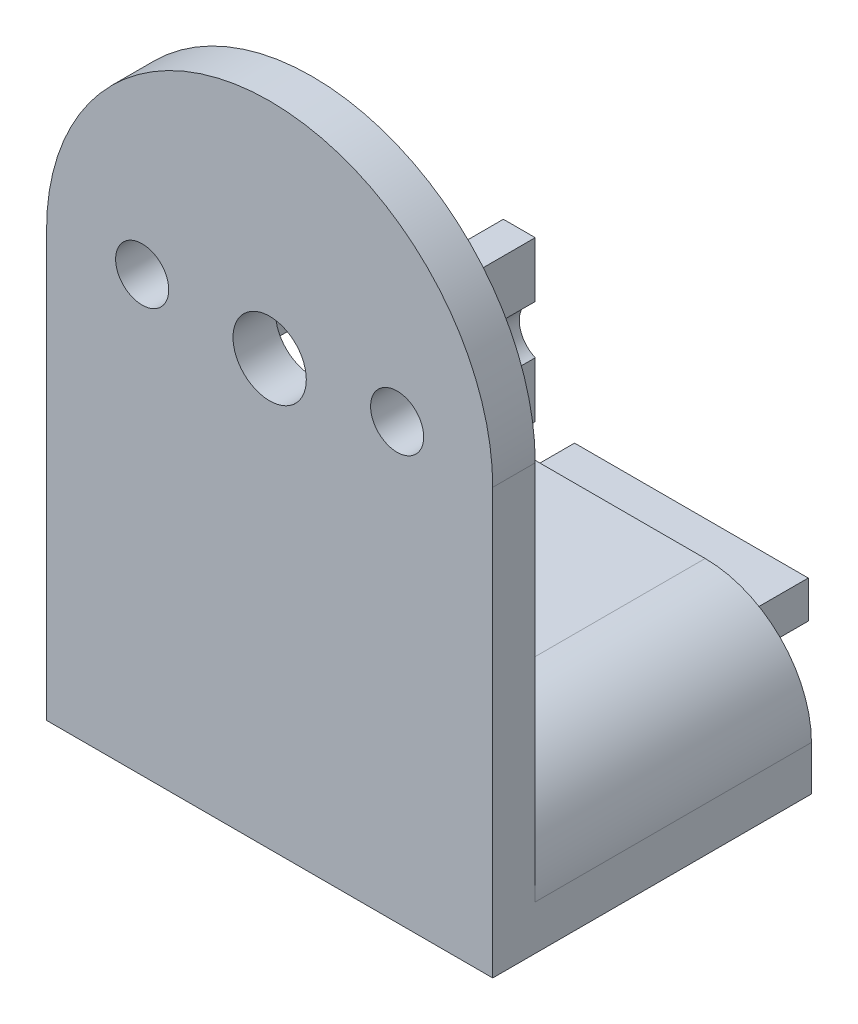
SolidWorks part; units mm, degrees
ref_plane "Front Plane" through (0, 0, 0) normal (0, 0, 1) x (1, 0, 0)
ref_plane "Top Plane" through (0, 0, 0) normal (0, 1, 0) x (1, 0, 0)
ref_plane "Right Plane" through (0, 0, 0) normal (1, 0, 0) x (0, 0, -1)
sketch "Sketch1" plane through (0, 0, 0) normal (0, 1, 0) x (1, 0, 0)
  line L0 (12.6055, 72.103) -> (12.6055, 7.103) construction
  line L1 (12.6055, 7.103) -> (-29.3945, 7.103)
  line L2 (12.6055, 7.103) -> (12.6055, -22.897)
  line L3 (12.6055, -22.897) -> (-29.3945, -22.897)
  line L4 (-29.3945, 7.103) -> (-29.3945, -22.897)
  line L5 (-29.3945, 72.103) -> (-29.3945, 7.103) construction
  point P0 (0, 0)
  dimension "D1" = 30
extrude "Boss-Extrude1" add sketch "Sketch1" along normal blind 11 and the other way blind 3.2
sketch "Sketch2" plane through (0, 0, -7.103) normal (0, 0, -1) x (-1, 0, 0)
  line L0 (-12.6055, -3.2) -> (29.3945, -3.2) construction
  line L1 (-2.6055, 4.5571) -> (19.3945, 4.5571)
  line L2 (-2.6055, 4.5571) -> (-2.6055, 1.044)
  line L3 (-2.6055, 1.044) -> (19.3945, 1.044)
  line L4 (19.3945, 4.5571) -> (19.3945, 1.044)
  line L5 (-12.6055, 11) -> (-12.6055, -3.2) construction
  line L6 (29.3945, 11) -> (29.3945, -3.2) construction
  line L7 (8.3945, 4.5571) -> (8.3945, 11)
  line L8 (-12.6055, 11) -> (29.3945, 11) construction
  point P0 (8.3945, 8)
  point P7 (8.3945, -3.2)
  dimension "D1" = 10
  dimension "D2" = 10
extrude "Boss-Extrude2" add sketch "Sketch2" along normal blind 9.7 contours L4 L1 L2 L3 region at (-8.3945, 2.8005, -7.103)
sketch "Sketch13" plane through (0, 0, 22.897) normal (0, 0, 1) x (1, 0, 0)
  line L1 (-29.3945, 11) -> (12.6055, 11)
  line L2 (-29.3945, 11) -> (-29.3945, 36.8)
  line L4 (12.6055, 11) -> (12.6055, 36.8)
  arc A0 (-29.3945, 36.8) -> (12.6055, 36.8) centre (-8.3945, 36.8) cw
  arc A1 (-10.2749, 41.5658) -> (-13.51, 37.0843) centre (-8.3945, 36.8) ccw construction
  circle A2 centre (-8.3945, 36.8) radius 3.45
  arc A3 (-5.7973, 39.0709) -> (-9.1816, 40.159) centre (-8.3945, 36.8) ccw construction
extrude "Boss-Extrude6" add sketch "Sketch13" against normal blind 4
sketch "Sketch14" plane through (0, 0, 18.897) normal (0, 0, -1) x (-1, 0, 0)
  line L1 (16.3945, 45.1553) -> (19.3945, 45.1553)
  line L2 (16.3945, 45.1553) -> (16.3945, 30.1553)
  line L3 (16.3945, 30.1553) -> (19.3945, 30.1553)
  line L4 (19.3945, 45.1553) -> (19.3945, 30.1553)
  line L5 (4.1722, 37.6553) -> (36.6168, 37.6553) construction
  circle A0 centre (8.3945, 36.8) radius 3.45 construction
  circle A1 centre (20.3945, 37.6553) radius 2.5
  point P8 (16.3945, 37.6553)
  dimension "D4" = 5
  dimension "D5" = 1
  dimension "D1" = 15
  dimension "D2" = 3
  dimension "D3" = 8
extrude "Boss-Extrude7" add sketch "Sketch14" along normal blind 10 contours L2 L5 A1 L4 L1 | L5 L2 L3 L4 A1 region at (-17.7855, 41.7568, 18.897) region at (-17.7855, 33.5537, 18.897)
extrude "Cut-Extrude4" cut sketch "Sketch14<5>" against normal up to next contours A1 L5 L4 | L5 A1 L4 | L5 L4 A1 | L4 L5 A1 region at (-20.9408, 38.7679, 18.897) region at (-18.7758, 38.5636, 18.897) region at (-18.7758, 36.747, 18.897) region at (-20.9408, 36.5427, 18.897)
sketch "Sketch14<5>" plane through (0, 0, 18.897) normal (0, 0, -1) x (-1, 0, 0) same geometry as "Sketch14"
ref_plane "Plane2" through (-8.3945, 0, 0) normal (-1, 0, 0) x (0, 0, 1)
mirror "Mirror1" about plane through (-8.3945, 0, 0) normal (-1, 0, 0) of "Cut-Extrude4", "Boss-Extrude7"
sketch "Sketch15" plane through (-16.3945, 0, 0) normal (1, 0, 0) x (0, 0, -1)
  circle A0 centre (-13.5581, 38.0239) radius 1.75
  dimension "D1" = 3.5
extrude "Cut-Extrude5" cut sketch "Sketch15" against normal through all both and the other way through all
fillet "Fillet3" radius 10 2 edges at (-29.3945, 11, 5.897) (12.6055, 11, 5.897)
